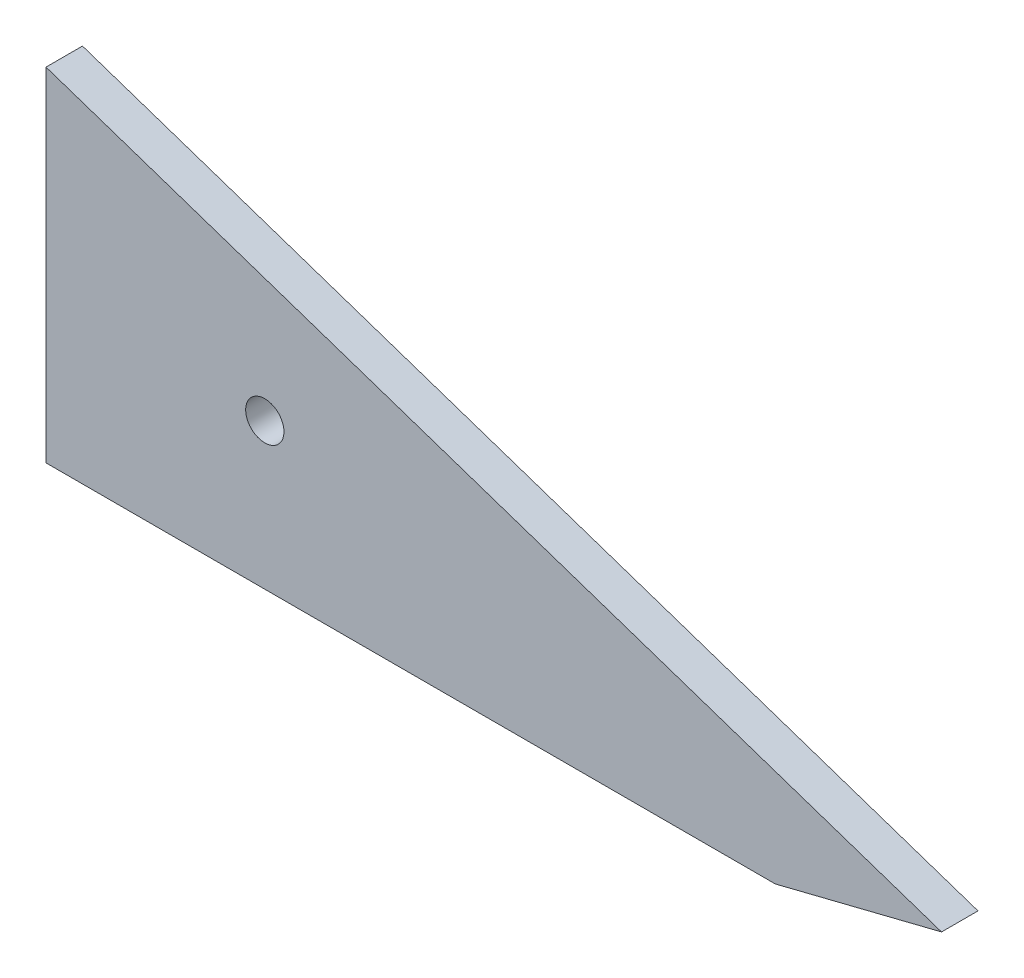
SolidWorks part; units mm, degrees
material "A516 Gr. 70 (Killed Carbon Steel)"
ref_plane "Front Plane" through (0, 0, 0) normal (0, 0, 1) x (1, 0, 0)
ref_plane "Top Plane" through (0, 0, 0) normal (0, 1, 0) x (1, 0, 0)
ref_plane "Right Plane" through (0, 0, 0) normal (1, 0, 0) x (0, 0, -1)
sketch "Sketch1" plane through (0, 0, 0) normal (0, 0, 1) x (1, 0, 0)
  line L0 (0, 0) -> (200, 0)
  line L1 (220, 5) -> (220, 20) construction
  line L2 (220, 20) -> (0, 94)
  line L3 (0, 94) -> (0, 0)
  line L4 (0, 0) -> (200, 0) construction
  line L5 (200, 0) -> (220, 5)
  line L6 (220, 0) -> (220, 5) construction
  line L7 (200, 0) -> (220, 0) construction
  line L8 (220, 5) -> (245.5814, 11.3953)
  line L9 (245.5814, 11.3953) -> (220, 20)
  dimension "D1" = 5
  dimension "D2" = 200
  dimension "D3" = 94
  dimension "D4" = 20
  dimension "D5" = 20
extrude "Boss-Extrude1" add sketch "Sketch1" along normal blind 10
hole_wizard "M12x1.5 Tapped Hole2" positions "3DSketch2" profile "Sketch6" tap size "M12x1.5" standard "ANSI Metric"
sketch3d "3DSketch2"
  line L0 (0, 0, 10) -> (200, 0, 10) construction
  line L1 (0, 94, 10) -> (0, 0, 10) construction
  point P0 (60, 40, 10)
  point P3 (0, 0, 0)
  point P4 (70.7332, 34.8125, 10)
  dimension "D1" = 60
  dimension "D2" = 40
sketch "Sketch6" plane through (60, 40, 10) normal (1, 0, 0) x (0, -1, 0)
  line L0 (0, 0) -> (0, 31.6545)
  line L1 (0, 31.6545) -> (5.25, 28.5)
  line L2 (5.25, 28.5) -> (5.25, 0)
  line L5 (5.25, 0) -> (0, 0)
  line L10 (0, 31.6545) -> (-5.25, 28.5) construction
  line L11 (0, -6.35) -> (0, 107.95) construction
  dimension "Tap Drill Dia." = 10.5
  dimension "Tap Drill Depth" = 28.5
  dimension "Drill Angle" = 118
cosmetic thread "Hole Thread2" parameters "D1"=24, "D2"=12
